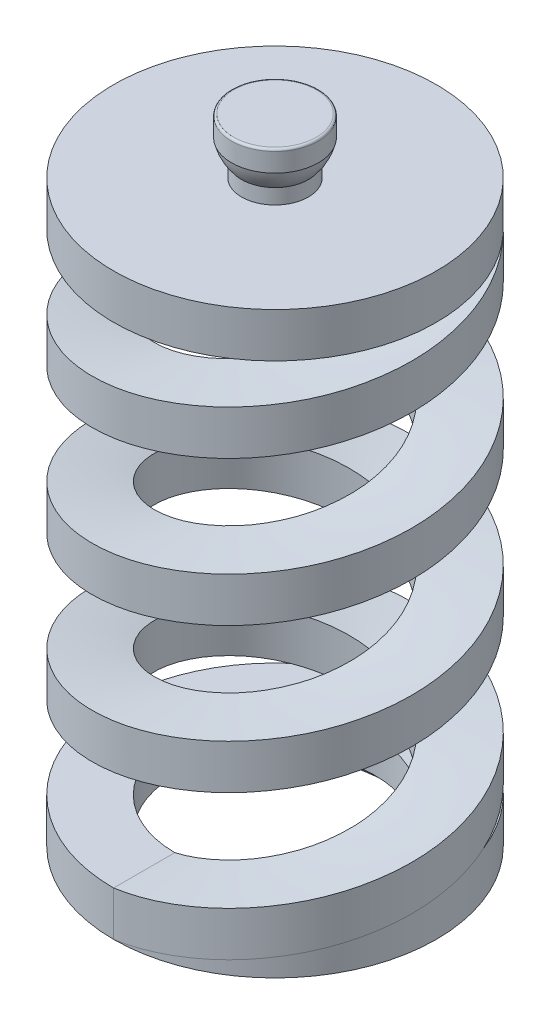
SolidWorks part; units mm, degrees
ref_plane "前视基准面" through (0, 0, 0) normal (0, 0, 1) x (1, 0, 0)
ref_plane "上视基准面" through (0, 0, 0) normal (0, 1, 0) x (1, 0, 0)
ref_plane "右视基准面" through (0, 0, 0) normal (1, 0, 0) x (0, 0, -1)
sketch "草图1" plane through (0, 0, 0) normal (0, 1, 0) x (1, 0, 0)
  circle A0 centre (0, 0) radius 5.875
  dimension "D1" = 11.75
curve "螺旋线/涡状线1" pitch 6.5 height 24.05 radius 5.875 centre (0, 0, 0) axis (0, 1, 0) start towards (0, 0, 1)
sketch "草图2" plane through (0, 0, 0) normal (1, 0, 0) x (0, 0, -1)
  line L0 (0, 0) -> (-5.875, 0) construction
  line L1 (-4.5, 1) -> (-4.5, -1)
  line L2 (-4.5, 1) -> (-7.25, 1)
  line L3 (-4.5, -1) -> (-7.25, -1)
  line L4 (-7.25, 1) -> (-7.25, -1)
  line L5 (-4.5, 1) -> (-7.25, -1) construction
  line L6 (-4.5, -1) -> (-7.25, 1) construction
  spline S0 degree 3 poles (-5.875, 0) (-5.875, 0.135) (-5.567, 0.408) (-4.2518, 0.8151) (-2.2849, 1.2229) (0.0321, 1.6305) (2.3442, 2.0381) (4.2971, 2.4458) (5.5913, 2.8534) (6.0287, 3.261) (5.542, 3.6686) (4.206, 4.0763) (2.2254, 4.4839) (-0.0963, 4.8915) (-2.4032, 5.2992) (-4.3419, 5.7068) (-5.615, 6.1144) (-6.0276, 6.522) (-5.5164, 6.9297) (-4.1598, 7.3373) (-2.1656, 7.7449) (0.1605, 8.1525) (2.462, 8.5602) (4.3862, 8.9678) (5.6381, 9.3754) (6.0259, 9.7831) (5.4902, 10.1907) (4.1131, 10.5983) (2.1056, 11.0059) (-0.2247, 11.4136) (-2.5205, 11.8212) (-4.43, 12.2288) (-5.6605, 12.6364) (-6.0235, 13.0441) (-5.4634, 13.4517) (-4.0659, 13.8593) (-2.0453, 14.2669) (0.2888, 14.6746) (2.5786, 15.0822) (4.4733, 15.4898) (5.6823, 15.8975) (6.0205, 16.3051) (5.4359, 16.7127) (4.0183, 17.1203) (1.9848, 17.528) (-0.3529, 17.9356) (-2.6365, 18.3432) (-4.516, 18.7508) (-5.7034, 19.1585) (-6.0167, 19.5661) (-5.4078, 19.9737) (-3.9702, 20.3814) (-1.924, 20.789) (0.417, 21.1966) (2.6941, 21.6042) (4.5583, 22.0119) (5.7239, 22.4195) (6.0124, 22.8271) (5.3786, 23.2349) (3.9237, 23.642) (2.5448, 23.915) (1.8155, 24.05) knots 0 0 0 0 0.016949 0.033898 0.050847 0.067797 0.084746 0.101695 0.118644 0.135593 0.152542 0.169492 0.186441 0.20339 0.220339 0.237288 0.254237 0.271186 0.288136 0.305085 0.322034 0.338983 0.355932 0.372881 0.389831 0.40678 0.423729 0.440678 0.457627 0.474576 0.491525 0.508475 0.525424 0.542373 0.559322 0.576271 0.59322 0.610169 0.627119 0.644068 0.661017 0.677966 0.694915 0.711864 0.728814 0.745763 0.762712 0.779661 0.79661 0.813559 0.830508 0.847458 0.864407 0.881356 0.898305 0.915254 0.932203 0.949153 0.966102 0.983051 1 1 1 1 construction
  dimension "D1" = 2
  dimension "D2" = 2.75
sweep "扫描1" add profiles "草图2" path "螺旋线/涡状线1"
ref_plane "基准面1" through (0, -1, 0) normal (0, 1, 0) x (1, 0, 0)
sketch "草图3" plane through (0, -1, 0) normal (0, 1, 0) x (1, 0, 0)
  circle A0 centre (0, 0) radius 7.25
  circle A1 centre (0, 0) radius 4.5
extrude "凸台-拉伸1" add sketch "草图3" along normal blind 2
ref_plane "基准面2" through (0, 25, 0) normal (0, 1, 0) x (1, 0, 0)
sketch "草图4" plane through (0, 25, 0) normal (0, 1, 0) x (1, 0, 0)
  circle A0 centre (0, 0) radius 7.25
  circle A1 centre (0, 0) radius 4.5
extrude "凸台-拉伸2" add sketch "草图4" against normal blind 2
sketch "草图5" plane through (0, 0, 0) normal (1, 0, 0) x (0, 0, -1)
  line L1 (7.25, 25) -> (-7.25, 25)
  line L2 (7.25, 25) -> (7.25, 25.5)
  line L3 (7.25, 25.5) -> (-7.25, 25.5)
  line L4 (-7.25, 25) -> (-7.25, 25.5)
  dimension "D1" = 0.5
  dimension "D2" = 14.5
extrude "切除-拉伸1" cut sketch "草图5" against normal up to next
sketch "草图6" plane through (0, 25, 0) normal (0, 1, 0) x (1, 0, 0)
  circle A0 centre (0, 0) radius 7.25
  dimension "D1" = 14.5
extrude "凸台-拉伸3" add sketch "草图6" against normal blind 1
sketch "草图7" plane through (0, 0, 0) normal (0, 0, 1) x (1, 0, 0)
  line L0 (0, 25) -> (0, 27) construction
  line L1 (7.25, 25) -> (-7.25, 25) construction
  line L2 (0, 27) -> (0, 27.5) construction
  line L3 (0, 27.5) -> (1.95, 27.5)
  line L4 (1.95, 27.5) -> (1.95, 26.5556)
  line L5 (0, 25) -> (1.5, 25)
  line L6 (1.5, 25) -> (1.5, 25.6771)
  line L7 (0, 25) -> (0, 27.5)
  arc A0 (1.5, 25.6771) -> (1.95, 26.5556) centre (0, 27) ccw
  dimension "D5" = 2
  dimension "D1" = 2
  dimension "D2" = 0.5
  dimension "D3" = 1.95
  dimension "D4" = 1.5
revolve "旋转1" add sketch "草图7" angle 360 about L7
fillet "圆角4" radius 0.1 1 edges at (1.95, 27.5, 0)
chamfer "倒角1" distance 0.5 angle 45 1 edges at (0, -1, 4.5)
